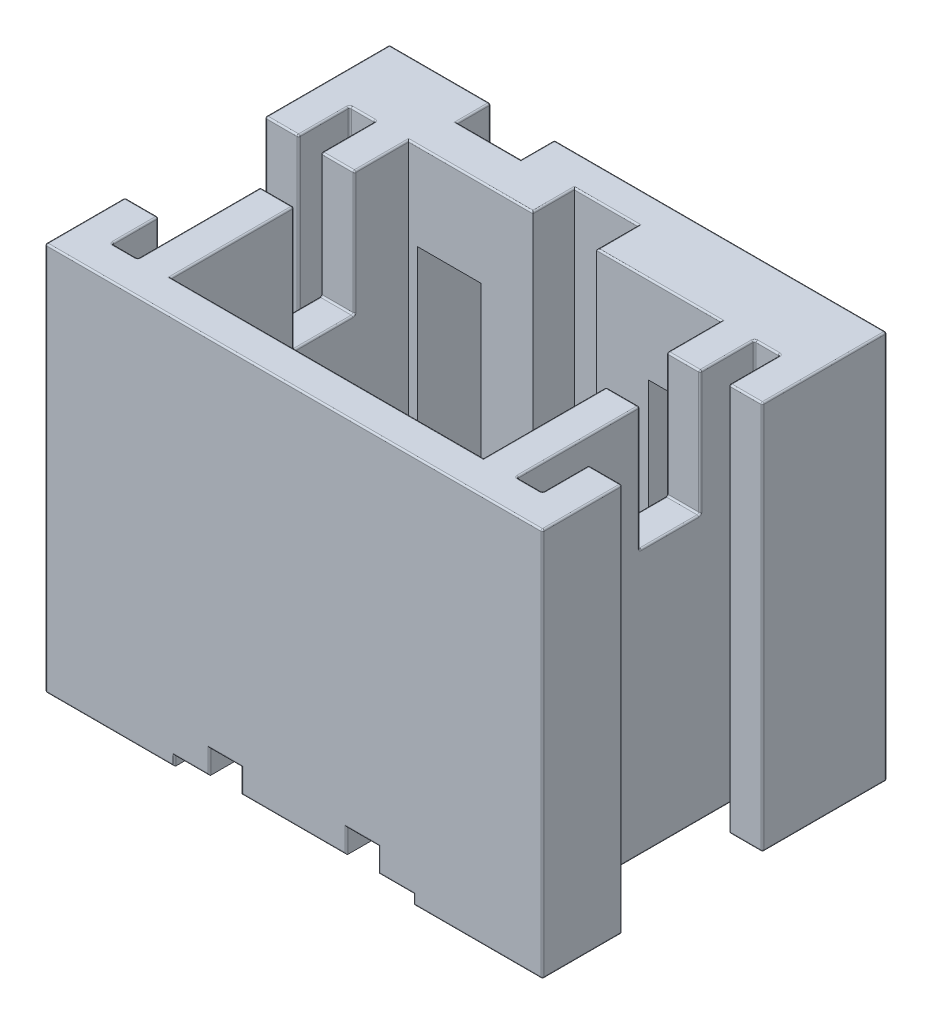
SolidWorks part; units mm, degrees
ref_plane "Front Plane" through (0, 0, 0) normal (0, 0, 1) x (1, 0, 0)
ref_plane "Top Plane" through (0, 0, 0) normal (0, 1, 0) x (1, 0, 0)
ref_plane "Right Plane" through (0, 0, 0) normal (1, 0, 0) x (0, 0, -1)
sketch "Sketch1" plane through (0, 0, 0) normal (0, 1, 0) x (1, 0, 0)
  line L1 (-3.9624, 2.7432) -> (3.9624, 2.7432)
  line L2 (-3.9624, 2.7432) -> (-3.9624, -2.7432)
  line L3 (-3.9624, -2.7432) -> (3.9624, -2.7432)
  line L4 (3.9624, 2.7432) -> (3.9624, -2.7432)
  line L5 (-3.9624, 2.7432) -> (3.9624, -2.7432) construction
  line L6 (-3.9624, -2.7432) -> (3.9624, 2.7432) construction
  point P0 (0, 0)
  dimension "D1" = 7.9248
  dimension "D2" = 5.4864
extrude "Boss-Extrude1" add sketch "Sketch1" along normal blind 6.1976
sketch "Sketch3" plane through (0, 6.1976, 0) normal (0, 1, 0) x (1, 0, 0)
  line L0 (-3.9624, 2.7432) -> (-3.9624, -2.7432) construction
  line L1 (-3.9624, 0.762) -> (-3.429, 0.762)
  line L2 (-3.9624, 0.762) -> (-3.9624, -1.4732)
  line L3 (-3.9624, -1.4732) -> (-3.429, -1.4732)
  line L4 (-3.429, 0.762) -> (-3.429, -1.4732) construction
  line L5 (-3.9624, -2.7432) -> (3.9624, -2.7432) construction
  line L6 (3.9624, 2.7432) -> (-3.9624, 2.7432) construction
  line L7 (-3.429, 1.5748) -> (-3.0226, 1.5748)
  line L8 (-3.429, 1.5748) -> (-3.429, 0.762)
  line L9 (-3.429, -2.2098) -> (-3.0226, -2.2098)
  line L10 (-3.0226, 1.5748) -> (-3.0226, -2.2098)
  line L11 (-3.429, -1.4732) -> (-3.429, -2.2098)
  line L12 (0, 2.7432) -> (0, -2.7432) construction
  line L13 (3.429, 0.762) -> (3.429, -1.4732) construction
  line L14 (3.429, -1.4732) -> (3.429, -2.2098)
  line L15 (3.0226, 1.5748) -> (3.0226, -2.2098)
  line L16 (3.429, -2.2098) -> (3.0226, -2.2098)
  line L17 (3.429, 1.5748) -> (3.429, 0.762)
  line L18 (3.429, 1.5748) -> (3.0226, 1.5748)
  line L19 (3.9624, -1.4732) -> (3.429, -1.4732)
  line L20 (3.9624, 0.762) -> (3.9624, -1.4732)
  line L21 (3.9624, 0.762) -> (3.429, 0.762)
  dimension "D1" = 2.2352
  dimension "D2" = 0.5334
  dimension "D3" = 1.27
  dimension "D4" = 0.5334
  dimension "D5" = 1.1684
  dimension "D6" = 0.4064
extrude "Cut-Extrude1" cut sketch "Sketch3" against normal through all
sketch "Sketch4" plane through (0, 6.1976, 0) normal (0, 1, 0) x (1, 0, 0)
  line L0 (0.508, 1.5748) -> (2.4892, 1.5748)
  line L1 (-2.4892, 1.5748) -> (-0.508, 1.5748)
  line L2 (-2.4892, 1.5748) -> (-2.4892, -2.2098)
  line L3 (-2.4892, -2.2098) -> (2.4892, -2.2098)
  line L4 (2.4892, 1.5748) -> (2.4892, -2.2098)
  line L5 (-3.0226, -2.2098) -> (-3.0226, 1.5748) construction
  line L6 (-0.508, 1.5748) -> (-0.508, 2.2352)
  line L7 (-0.508, 2.2352) -> (0.508, 2.2352)
  line L8 (0.508, 1.5748) -> (0.508, 2.2352)
  line L9 (-3.429, -2.2098) -> (-3.0226, -2.2098) construction
  line L10 (-3.0226, 1.5748) -> (-3.429, 1.5748) construction
  line L11 (3.9624, 2.7432) -> (-3.9624, 2.7432) construction
  point P8 (0, 2.2352)
  point P10 (0, -2.2098)
  dimension "D1" = 0.5334
  dimension "D2" = 0.508
  dimension "D3" = 1.016
extrude "Cut-Extrude2" cut sketch "Sketch4" against normal blind 4.3434
sketch "Sketch5" plane through (0, 0, -2.7432) normal (0, 0, -1) x (-1, 0, 0)
  line L0 (-3.9624, 0) -> (3.9624, 0) construction
  line L1 (-2.3495, 0) -> (-1.3335, 0)
  line L2 (-2.3495, 0) -> (-2.3495, 4.8006)
  line L3 (-2.3495, 4.8006) -> (-1.3335, 4.8006)
  line L4 (-1.3335, 0) -> (-1.3335, 4.8006)
  line L5 (-1.3335, 4.8006) -> (1.3335, 4.8006) construction
  line L6 (1.3335, 0) -> (2.3495, 0)
  line L7 (1.3335, 0) -> (1.3335, 4.8006)
  line L8 (1.3335, 4.8006) -> (2.3495, 4.8006)
  line L9 (2.3495, 0) -> (2.3495, 4.8006)
  line L10 (-3.9624, 6.1976) -> (3.9624, 6.1976) construction
  point P10 (0, 4.8006)
  dimension "D1" = 1.016
  dimension "D2" = 2.667
  dimension "D3" = 1.397
extrude "Cut-Extrude3" cut sketch "Sketch5" against normal up to surface (1.1684 mm away) up to face at (-1.4986, 4.0259, -1.5748)
sketch "Sketch6" plane through (0, 6.1976, 0) normal (0, 1, 0) x (1, 0, 0)
  line L0 (3.9624, 2.7432) -> (-3.9624, 2.7432) construction
  line L1 (-2.3495, 2.7432) -> (-1.3335, 2.7432)
  line L2 (-2.3495, 2.7432) -> (-2.3495, 2.2098)
  line L3 (-2.3495, 2.2098) -> (-1.3335, 2.2098)
  line L4 (-1.3335, 2.7432) -> (-1.3335, 2.2098)
  line L5 (-2.3495, 2.7432) -> (-1.3335, 2.7432) construction
  dimension "D1" = 0.5334
extrude "Cut-Extrude4" cut sketch "Sketch6" against normal offset from surface (0.6096 mm away) 0.7874 up to face at (-1.8415, 4.8006, -2.159)
sketch "Sketch7" plane through (0, 0, 0) normal (1, 0, 0) x (0, 0, -1)
  line L0 (1.5748, 6.1976) -> (-2.2098, 6.1976) construction
  line L1 (-0.254, 6.1976) -> (0.7112, 6.1976)
  line L2 (-0.254, 6.1976) -> (-0.254, 4.2164)
  line L3 (-0.254, 4.2164) -> (0.7112, 4.2164)
  line L4 (0.7112, 6.1976) -> (0.7112, 4.2164)
  line L5 (2.7432, 6.1976) -> (2.7432, 0) construction
  line L6 (-2.7432, 6.1976) -> (-2.7432, 0) construction
  dimension "D1" = 2.032
  dimension "D2" = 2.4892
  dimension "D3" = 1.9812
extrude "Cut-Extrude5" cut sketch "Sketch7" against normal through all both and the other way through all
sketch "Sketch8" plane through (0, 1.8542, 0) normal (0, 1, 0) x (1, 0, 0)
  line L0 (-2.4892, -2.2098) -> (2.4892, -2.2098) construction
  line L1 (-0.1016, -2.0828) -> (0.1016, -2.0828)
  line L2 (-0.1016, -2.0828) -> (-0.1016, -2.2098)
  line L3 (-0.1016, -2.2098) -> (0.1016, -2.2098)
  line L4 (0.1016, -2.0828) -> (0.1016, -2.2098)
  point P6 (0, -2.0828)
  point P8 (-0.1203, -2.0721)
  dimension "D1" = 0.2032
  dimension "D2" = 0.127
extrude "Boss-Extrude2" add sketch "Sketch8" along normal offset from surface (2.5654 mm away) 1.778 up to face at (-0.3069, 6.1976, -1.5981)
sketch "Sketch9" plane through (0, 0, 2.7432) normal (0, 0, 1) x (1, 0, 0)
  line L0 (-3.9624, 0) -> (3.9624, 0) construction
  line L1 (-1.905, 0) -> (1.905, 0)
  line L2 (-1.905, 0) -> (-1.905, 0.1524)
  line L3 (-1.905, 0.1524) -> (-1.3462, 0.1524)
  line L4 (1.905, 0) -> (1.905, 0.1524)
  line L5 (-0.8382, 0.1524) -> (0.8382, 0.1524)
  line L7 (0.8382, 0.1524) -> (0.8382, 0.5334)
  line L8 (0.8382, 0.5334) -> (1.3462, 0.5334)
  line L9 (1.3462, 0.1524) -> (1.3462, 0.5334)
  line L10 (1.3462, 0.1524) -> (1.905, 0.1524)
  line L11 (-0.8382, 0.1524) -> (-0.8382, 0.5334)
  line L12 (-0.8382, 0.5334) -> (-1.3462, 0.5334)
  line L13 (-1.3462, 0.1524) -> (-1.3462, 0.5334)
  point P14 (0, 0.1524)
  point P15 (0, 0)
  point P16 (3.0716, 0.4671)
  point P17 (-11.2907, 0.2761)
  dimension "D1" = 3.81
  dimension "D2" = 2.6924
  dimension "D3" = 0.1524
  dimension "D4" = 0.508
  dimension "D5" = 0.381
extrude "Cut-Extrude6" cut sketch "Sketch9" against normal blind 3.302
sketch "Sketch10" plane through (0, 1.8542, 0) normal (0, 1, 0) x (1, 0, 0)
  line L0 (1.3335, 1.5748) -> (0.508, 1.5748) construction
  line L1 (-1.8457, -0.3175) -> (-0.3217, -0.3175)
  line L2 (-1.8457, -0.3175) -> (-1.8457, 1.5748)
  line L3 (-1.8457, 1.5748) -> (-0.508, 1.5748)
  line L4 (-0.3217, -0.3175) -> (-0.3217, 1.5748)
  line L5 (1.8457, -0.3175) -> (0.3217, -0.3175)
  line L6 (1.8457, -0.3175) -> (1.8457, 1.5748)
  line L7 (1.8457, 1.5748) -> (0.508, 1.5748)
  line L8 (0.3217, -0.3175) -> (0.3217, 1.5748)
  line L9 (-0.3217, -0.3175) -> (0.3217, -0.3175) construction
  line L10 (-1.8457, -0.3175) -> (-2.4892, -0.3175) construction
  line L11 (2.4892, -0.254) -> (2.4892, 0.7112) construction
  line L12 (-2.4892, 0.7112) -> (-2.4892, -0.254) construction
  line L13 (2.4892, -0.3175) -> (1.8457, -0.3175) construction
  line L14 (-2.4892, 1.5748) -> (-2.4892, -2.2098) construction
  line L17 (-0.3217, 1.5748) -> (-0.3217, 2.2352)
  line L18 (-0.3217, 2.2352) -> (-0.508, 2.2352)
  line L19 (-0.508, 1.5748) -> (-0.508, 2.2352)
  line L20 (0.508, 2.2352) -> (0.3217, 2.2352)
  line L21 (0.508, 2.2352) -> (0.508, 1.5748)
  line L23 (0.3217, 2.2352) -> (0.3217, 1.5748)
  point P10 (0, -0.3175)
  point P19 (0, 0)
  point P22 (-2.4892, -0.3175)
  dimension "D1" = 1.524
extrude "Boss-Extrude3" add sketch "Sketch10" along normal blind 0.508
chamfer "Chamfer1" distance 0.381 angle 60 2 edges at (1.0837, 1.8542, 0.3175) (-1.0837, 1.8542, 0.3175) first distance on face at (0, 1.8542, 0.0198)
fillet "Fillet1" radius 0.0254 119 edges at (2.4892, 5.207, 0.254) (2.4892, 5.207, -0.7112) (-2.4892, 5.207, -0.7112) (-2.4892, 5.207, 0.254) (2.7559, 4.2164, 0.254) (2.4892, 4.2164, -0.2286) (2.7559, 4.2164, -0.7112) (-2.7559, 4.2164, -0.7112) (-2.4892, 4.2164, -0.2286) (-2.7559, 4.2164, 0.254) (-3.429, 0, -1.1684) (-3.429, 0, 1.8415) (3.429, 0, -1.1684) (3.429, 3.0988, -1.5748) (3.2258, 0, -1.5748) (3.429, 0, 1.8415) (3.2258, 0, 2.2098) (3.429, 3.0988, 2.2098) (3.429, 3.0988, 1.4732) (3.6957, 0, 1.4732) (3.6957, 0, -0.762) (3.429, 3.0988, -0.762) (3.9624, 3.0988, 1.4732) (3.9624, 0, 2.1082) (3.9624, 0, -1.7526) (3.9624, 3.0988, -0.762) (3.0226, 5.207, -0.7112) (3.0226, 3.0988, -1.5748) (3.0226, 0, 0.3175) (3.0226, 3.0988, 2.2098) (3.0226, 5.207, 0.254) (3.0226, 4.2164, -0.2286) (-3.156, 0, -2.7432) (-2.3495, 2.4003, -2.7432) (-1.8415, 4.8006, -2.7432) (-1.3335, 2.4003, -2.7432) (0, 0, -2.7432) (1.3335, 2.4003, -2.7432) (1.8415, 4.8006, -2.7432) (2.3495, 2.4003, -2.7432) (3.1559, 0, -2.7432) (3.9624, 3.0988, -2.7432) (-1.3335, 5.8928, -2.7432) (-1.8415, 5.588, -2.7432) (-2.3495, 5.8928, -2.7432) (-3.6957, 0, 1.4732) (-3.429, 3.0988, 1.4732) (-3.429, 3.0988, 2.2098) (-3.2258, 0, 2.2098) (-3.2258, 0, -1.5748) (-3.429, 3.0988, -1.5748) (3.9624, 3.0988, 2.7432) (2.9337, 0, 2.7432) (1.905, 0.0762, 2.7432) (1.6256, 0.1524, 2.7432) (1.3462, 0.3429, 2.7432) (1.0922, 0.5334, 2.7432) (0.8382, 0.3429, 2.7432) (0, 0.1524, 2.7432) (-0.8382, 0.3429, 2.7432) (-1.0922, 0.5334, 2.7432) (-1.3462, 0.3429, 2.7432) (-1.6256, 0.1524, 2.7432) (-1.905, 0.0762, 2.7432) (-2.9337, 0, 2.7432) (-3.0226, 3.0988, 2.2098) (-3.0226, 0, 0.3175) (-3.0226, 3.0988, -1.5748) (-3.0226, 5.207, -0.7112) (-3.0226, 4.2164, -0.2286) (-3.0226, 5.207, 0.254) (-3.429, 3.0988, -0.762) (-3.6957, 0, -0.762) (-3.9624, 3.0988, -2.7432) (-3.9624, 3.0988, -0.762) (-3.9624, 0, -1.7526) (-3.9624, 3.0988, 2.7432) (-3.9624, 0, 2.1082) (-3.9624, 3.0988, 1.4732) (-2.4892, 6.1976, 1.2319) (0, 6.1976, 2.2098) (2.4892, 6.1976, 1.2319) (2.7559, 6.1976, 0.254) (3.0226, 6.1976, 1.2319) (3.2258, 6.1976, 2.2098) (3.429, 6.1976, 1.8415) (3.6957, 6.1976, 1.4732) (3.9624, 6.1976, 2.1082) (0, 6.1976, 2.7432) (-3.9624, 6.1976, 2.1082) (-3.6957, 6.1976, 1.4732) (-3.429, 6.1976, 1.8415) (-3.2258, 6.1976, 2.2098) (-3.0226, 6.1976, 1.2319) (-2.7559, 6.1976, 0.254) (2.4892, 6.1976, -1.143) (1.4986, 6.1976, -1.5748) (0.508, 6.1976, -1.905) (0, 6.1976, -2.2352) (-0.508, 6.1976, -1.905) (-1.4986, 6.1976, -1.5748) (-2.4892, 6.1976, -1.143) (-2.7559, 6.1976, -0.7112) (-3.0226, 6.1976, -1.143) (-3.2258, 6.1976, -1.5748) (-3.429, 6.1976, -1.1684) (-3.6957, 6.1976, -0.762) (-3.9624, 6.1976, -1.7526) (-3.156, 6.1976, -2.7432) (-2.3495, 6.1976, -2.4765) (-1.8415, 6.1976, -2.2098) (-1.3335, 6.1976, -2.4765) (1.3144, 6.1976, -2.7432) (3.9624, 6.1976, -1.7526) (3.6957, 6.1976, -0.762) (3.429, 6.1976, -1.1684) (3.2258, 6.1976, -1.5748) (3.0226, 6.1976, -1.143) (2.7559, 6.1976, -0.7112)
sketch "Sketch11" plane through (0, 2.3622, 0) normal (0, 1, 0) x (1, 0, 0)
  line L0 (-0.9144, 0.5207) -> (0.9144, 0.5207) construction
  line L1 (-0.9144, 0.5207) -> (-1.27, 0.5207)
  line L2 (-0.9144, 0.5207) -> (-0.9144, 0.1651)
  line L3 (-0.9144, 0.1651) -> (-1.27, 0.1651)
  line L4 (-1.27, 0.5207) -> (-1.27, 0.1651)
  line L5 (1.27, 0.5207) -> (0.9144, 0.5207)
  line L6 (1.27, 0.5207) -> (1.27, 0.1651)
  line L7 (1.27, 0.1651) -> (0.9144, 0.1651)
  line L8 (0.9144, 0.5207) -> (0.9144, 0.1651)
  line L9 (-1.3081, 2.7432) -> (3.937, 2.7432) construction
  point P8 (0, 0.5207)
  dimension "D1" = 0.3556
  dimension "D2" = 2.54
  dimension "D3" = 2.5781
extrude "Cut-Extrude7" cut sketch "Sketch11" against normal through all
